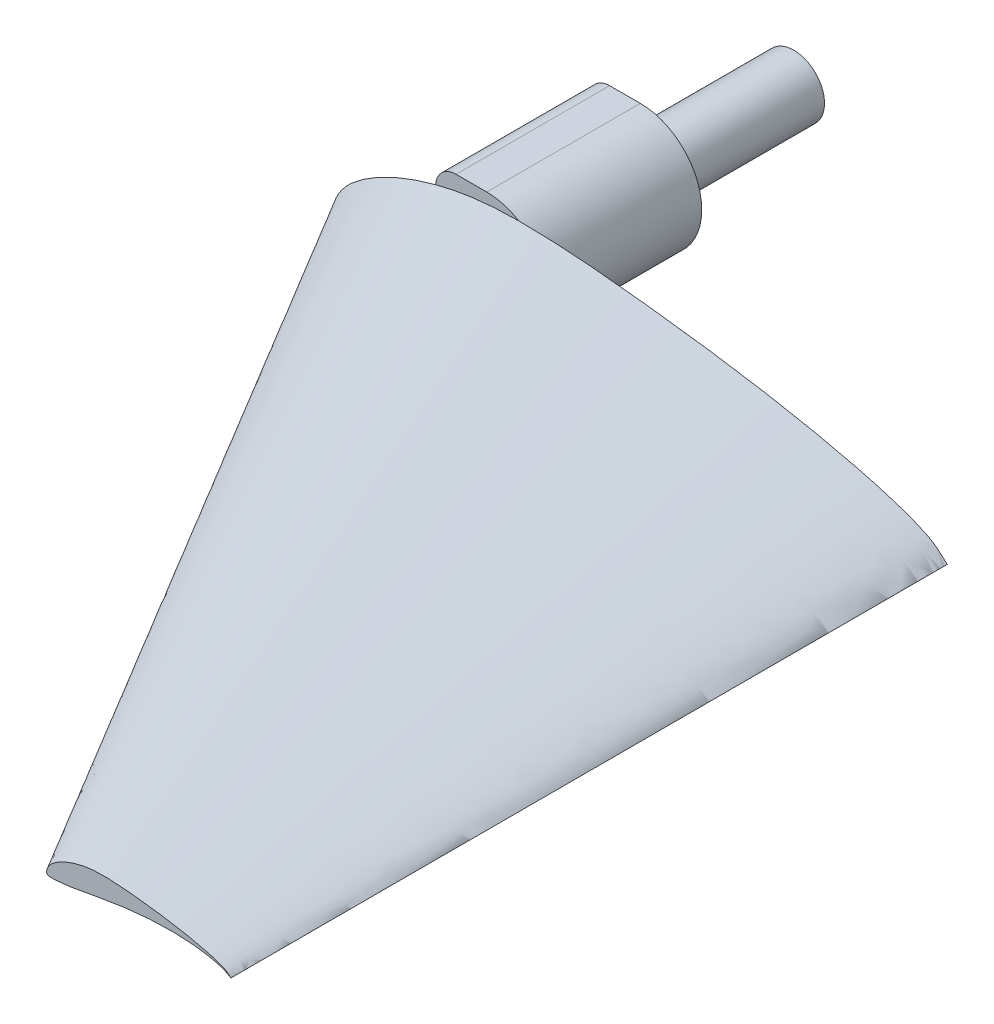
SolidWorks part; units mm, degrees
material "Nylon 101"
ref_plane "Front Plane" through (0, 0, 0) normal (0, 0, 1) x (1, 0, 0)
ref_plane "Top Plane" through (0, 0, 0) normal (0, 1, 0) x (1, 0, 0)
ref_plane "Right Plane" through (0, 0, 0) normal (1, 0, 0) x (0, 0, -1)
curve "Curve1"
  spline degree 3 poles (59.7678, 0.1558, 0) (60.0544, -0.0387, 0) (59.8031, 0.1485, 0) (59.6363, 0.3122, 0) (59.2659, 0.654, 0) (58.8289, 1.0177, 0) (58.2312, 1.3843, 0) (57.4879, 1.7396, 0) (56.5906, 2.1104, 0) (55.5406, 2.4917, 0) (54.3427, 2.8798, 0) (53.0045, 3.2753, 0) (51.5282, 3.6599, 0) (49.9319, 4.0656, 0) (48.2145, 4.4525, 0) (46.3922, 4.8372, 0) (44.4742, 5.2122, 0) (42.4721, 5.5744, 0) (40.3983, 5.9229, 0) (38.265, 6.2533, 0) (36.0858, 6.5663, 0) (33.8748, 6.8594, 0) (31.648, 7.1315, 0) (29.423, 7.3848, 0) (27.2185, 7.6127, 0) (25.0523, 7.811, 0) (22.9397, 7.9686, 0) (20.8927, 8.077, 0) (18.9227, 8.1238, 0) (17.0399, 8.1188, 0) (15.2476, 8.0266, 0) (13.5454, 7.8398, 0) (11.9261, 7.5756, 0) (10.3894, 7.2334, 0) (8.937, 6.8321, 0) (7.5748, 6.3788, 0) (6.3088, 5.8842, 0) (5.1469, 5.3508, 0) (4.0926, 4.7895, 0) (3.1518, 4.2068, 0) (2.3304, 3.6104, 0) (1.6286, 3.013, 0) (1.0568, 2.4081, 0) (0.6175, 1.801, 0) (0.293, 1.2104, 0) (0.0851, 0.6496, 0) (-0.014, 0.132, 0) (0.0051, -0.3058, 0) (0.1178, -0.7073, 0) (0.5368, -0.9066, 0) (1.1, -0.9346, 0) (1.8706, -0.9617, 0) (2.8397, -0.9199, 0) (3.9962, -0.8431, 0) (5.3274, -0.7201, 0) (6.8197, -0.5537, 0) (8.4657, -0.3402, 0) (10.2646, -0.0419, 0) (12.2253, 0.3321, 0) (14.3574, 0.7392, 0) (16.6507, 1.169, 0) (19.0906, 1.6038, 0) (21.6593, 2.0271, 0) (24.3369, 2.4248, 0) (27.1002, 2.7825, 0) (29.9244, 3.0895, 0) (32.7828, 3.3322, 0) (35.6468, 3.5043, 0) (38.4864, 3.5989, 0) (41.2709, 3.6108, 0) (43.9691, 3.5393, 0) (46.5501, 3.386, 0) (48.983, 3.153, 0) (51.2388, 2.849, 0) (53.288, 2.483, 0) (55.1067, 2.0673, 0) (56.6613, 1.6224, 0) (57.9337, 1.1476, 0) (58.8414, 0.7131, 0) (59.5107, 0.3113, 0) (59.7678, 0.1558, 0) (60.0544, -0.0387, 0) (59.8031, 0.1485, 0) knots -0.009748 -0.004147 -0.001 0 0.00098 0.003649 0.007484 0.012095 0.017526 0.024052 0.031783 0.040678 0.05071 0.061833 0.073978 0.087118 0.101144 0.11599 0.13157 0.147788 0.16455 0.181757 0.199311 0.217095 0.23499 0.252856 0.27054 0.287886 0.304773 0.321101 0.336806 0.3518 0.366031 0.379615 0.392653 0.40517 0.417171 0.428603 0.439419 0.449596 0.459102 0.467907 0.475988 0.483309 0.489874 0.495803 0.501149 0.505903 0.510046 0.513579 0.516447 0.51935 0.523823 0.529973 0.537715 0.546968 0.557637 0.56962 0.582804 0.597247 0.613135 0.630443 0.649056 0.668822 0.689595 0.711189 0.733426 0.756094 0.778988 0.80189 0.824566 0.846792 0.868338 0.888978 0.908492 0.926659 0.943286 0.958169 0.971136 0.981956 0.990252 0.995853 0.999 1 1.00098 1.003649 1.007484 periodic
sketch "Sketch2" plane through (0, 0, 0) normal (0, 0, 1) x (1, 0, 0)
  spline S0 degree 3 poles (59.7678, 0.1558) (60.0544, -0.0387) (59.8031, 0.1485) (59.6363, 0.3122) (59.2659, 0.654) (58.8289, 1.0177) (58.2312, 1.3843) (57.4879, 1.7396) (56.5906, 2.1104) (55.5406, 2.4917) (54.3427, 2.8798) (53.0045, 3.2753) (51.5282, 3.6599) (49.9319, 4.0656) (48.2145, 4.4525) (46.3922, 4.8372) (44.4742, 5.2122) (42.4721, 5.5744) (40.3983, 5.9229) (38.265, 6.2533) (36.0858, 6.5663) (33.8748, 6.8594) (31.648, 7.1315) (29.423, 7.3848) (27.2185, 7.6127) (25.0523, 7.811) (22.9397, 7.9686) (20.8927, 8.077) (18.9227, 8.1238) (17.0399, 8.1188) (15.2476, 8.0266) (13.5454, 7.8398) (11.9261, 7.5756) (10.3894, 7.2334) (8.937, 6.8321) (7.5748, 6.3788) (6.3088, 5.8842) (5.1469, 5.3508) (4.0926, 4.7895) (3.1518, 4.2068) (2.3304, 3.6104) (1.6286, 3.013) (1.0568, 2.4081) (0.6175, 1.801) (0.293, 1.2104) (0.0851, 0.6496) (-0.014, 0.132) (0.0051, -0.3058) (0.1178, -0.7073) (0.5368, -0.9066) (1.1, -0.9346) (1.8706, -0.9617) (2.8397, -0.9199) (3.9962, -0.8431) (5.3274, -0.7201) (6.8197, -0.5537) (8.4657, -0.3402) (10.2646, -0.0419) (12.2253, 0.3321) (14.3574, 0.7392) (16.6507, 1.169) (19.0906, 1.6038) (21.6593, 2.0271) (24.3369, 2.4248) (27.1002, 2.7825) (29.9244, 3.0895) (32.7828, 3.3322) (35.6468, 3.5043) (38.4864, 3.5989) (41.2709, 3.6108) (43.9691, 3.5393) (46.5501, 3.386) (48.983, 3.153) (51.2388, 2.849) (53.288, 2.483) (55.1067, 2.0673) (56.6613, 1.6224) (57.9337, 1.1476) (58.8414, 0.7131) (59.5107, 0.3113) (59.7678, 0.1558) (60.0544, -0.0387) (59.8031, 0.1485) knots -0.009748 -0.004147 -0.001 0 0.00098 0.003649 0.007484 0.012095 0.017526 0.024052 0.031783 0.040678 0.05071 0.061833 0.073978 0.087118 0.101144 0.11599 0.13157 0.147788 0.16455 0.181757 0.199311 0.217095 0.23499 0.252856 0.27054 0.287886 0.304773 0.321101 0.336806 0.3518 0.366031 0.379615 0.392653 0.40517 0.417171 0.428603 0.439419 0.449596 0.459102 0.467907 0.475988 0.483309 0.489874 0.495803 0.501149 0.505903 0.510046 0.513579 0.516447 0.51935 0.523823 0.529973 0.537715 0.546968 0.557637 0.56962 0.582804 0.597247 0.613135 0.630443 0.649056 0.668822 0.689595 0.711189 0.733426 0.756094 0.778988 0.80189 0.824566 0.846792 0.868338 0.888978 0.908492 0.926659 0.943286 0.958169 0.971136 0.981956 0.990252 0.995853 0.999 1 1.00098 1.003649 1.007484 only from (60, 0) to (60, 0) construction
  spline S1 degree 3 poles (59.7678, 0.1558) (60.0544, -0.0387) (59.8031, 0.1485) (59.6363, 0.3122) (59.2659, 0.654) (58.8289, 1.0177) (58.2312, 1.3843) (57.4879, 1.7396) (56.5906, 2.1104) (55.5406, 2.4917) (54.3427, 2.8798) (53.0045, 3.2753) (51.5282, 3.6599) (49.9319, 4.0656) (48.2145, 4.4525) (46.3922, 4.8372) (44.4742, 5.2122) (42.4721, 5.5744) (40.3983, 5.9229) (38.265, 6.2533) (36.0858, 6.5663) (33.8748, 6.8594) (31.648, 7.1315) (29.423, 7.3848) (27.2185, 7.6127) (25.0523, 7.811) (22.9397, 7.9686) (20.8927, 8.077) (18.9227, 8.1238) (17.0399, 8.1188) (15.2476, 8.0266) (13.5454, 7.8398) (11.9261, 7.5756) (10.3894, 7.2334) (8.937, 6.8321) (7.5748, 6.3788) (6.3088, 5.8842) (5.1469, 5.3508) (4.0926, 4.7895) (3.1518, 4.2068) (2.3304, 3.6104) (1.6286, 3.013) (1.0568, 2.4081) (0.6175, 1.801) (0.293, 1.2104) (0.0851, 0.6496) (-0.014, 0.132) (0.0051, -0.3058) (0.1178, -0.7073) (0.5368, -0.9066) (1.1, -0.9346) (1.8706, -0.9617) (2.8397, -0.9199) (3.9962, -0.8431) (5.3274, -0.7201) (6.8197, -0.5537) (8.4657, -0.3402) (10.2646, -0.0419) (12.2253, 0.3321) (14.3574, 0.7392) (16.6507, 1.169) (19.0906, 1.6038) (21.6593, 2.0271) (24.3369, 2.4248) (27.1002, 2.7825) (29.9244, 3.0895) (32.7828, 3.3322) (35.6468, 3.5043) (38.4864, 3.5989) (41.2709, 3.6108) (43.9691, 3.5393) (46.5501, 3.386) (48.983, 3.153) (51.2388, 2.849) (53.288, 2.483) (55.1067, 2.0673) (56.6613, 1.6224) (57.9337, 1.1476) (58.8414, 0.7131) (59.5107, 0.3113) (59.7678, 0.1558) (60.0544, -0.0387) (59.8031, 0.1485) knots -0.009748 -0.004147 -0.001 0 0.00098 0.003649 0.007484 0.012095 0.017526 0.024052 0.031783 0.040678 0.05071 0.061833 0.073978 0.087118 0.101144 0.11599 0.13157 0.147788 0.16455 0.181757 0.199311 0.217095 0.23499 0.252856 0.27054 0.287886 0.304773 0.321101 0.336806 0.3518 0.366031 0.379615 0.392653 0.40517 0.417171 0.428603 0.439419 0.449596 0.459102 0.467907 0.475988 0.483309 0.489874 0.495803 0.501149 0.505903 0.510046 0.513579 0.516447 0.51935 0.523823 0.529973 0.537715 0.546968 0.557637 0.56962 0.582804 0.597247 0.613135 0.630443 0.649056 0.668822 0.689595 0.711189 0.733426 0.756094 0.778988 0.80189 0.824566 0.846792 0.868338 0.888978 0.908492 0.926659 0.943286 0.958169 0.971136 0.981956 0.990252 0.995853 0.999 1 1.00098 1.003649 1.007484 only from (60, 0) to (60, 0)
ref_plane "Plane1" through (0, 0, 70) normal (0, 0, 1) x (1, 0, 0)
sketch "Sketch3" plane through (0, 0, 70) normal (0, 0, 1) x (1, 0, 0)
  spline S1 degree 3 poles (59.9303, 0.0467) (60.0163, -0.0116) (59.9409, 0.0445) (59.8909, 0.0936) (59.7798, 0.1962) (59.6487, 0.3053) (59.4694, 0.4153) (59.2464, 0.5219) (58.9772, 0.6331) (58.6622, 0.7475) (58.3028, 0.864) (57.9013, 0.9826) (57.4585, 1.098) (56.9796, 1.2197) (56.4644, 1.3358) (55.9177, 1.4512) (55.3423, 1.5636) (54.7416, 1.6723) (54.1195, 1.7769) (53.4795, 1.876) (52.8258, 1.9699) (52.1624, 2.0578) (51.4944, 2.1395) (50.8269, 2.2154) (50.1655, 2.2838) (49.5157, 2.3433) (48.8819, 2.3906) (48.2678, 2.4231) (47.6768, 2.4371) (47.112, 2.4356) (46.5743, 2.408) (46.0636, 2.3519) (45.5778, 2.2727) (45.1168, 2.17) (44.6811, 2.0496) (44.2724, 1.9136) (43.8927, 1.7653) (43.5441, 1.6052) (43.2278, 1.4369) (42.9455, 1.262) (42.6991, 1.0831) (42.4886, 0.9039) (42.317, 0.7224) (42.1852, 0.5403) (42.0879, 0.3631) (42.0255, 0.1949) (41.9958, 0.0396) (42.0015, -0.0917) (42.0353, -0.2122) (42.161, -0.272) (42.33, -0.2804) (42.5612, -0.2885) (42.8519, -0.276) (43.1989, -0.2529) (43.5982, -0.216) (44.0459, -0.1661) (44.5397, -0.1021) (45.0794, -0.0126) (45.6676, 0.0996) (46.3072, 0.2218) (46.9952, 0.3507) (47.7272, 0.4811) (48.4978, 0.6081) (49.3011, 0.7275) (50.13, 0.8347) (50.9773, 0.9269) (51.8348, 0.9997) (52.694, 1.0513) (53.5459, 1.0797) (54.3813, 1.0833) (55.1907, 1.0618) (55.965, 1.0158) (56.6949, 0.9459) (57.3716, 0.8547) (57.9864, 0.7449) (58.532, 0.6202) (58.9984, 0.4867) (59.3801, 0.3443) (59.6524, 0.2139) (59.8532, 0.0934) (59.9303, 0.0467) (60.0163, -0.0116) (59.9409, 0.0445) knots -0.009748 -0.004147 -0.001 0 0.00098 0.003649 0.007484 0.012095 0.017526 0.024052 0.031783 0.040678 0.05071 0.061833 0.073978 0.087118 0.101144 0.11599 0.13157 0.147788 0.16455 0.181757 0.199311 0.217095 0.23499 0.252856 0.27054 0.287886 0.304773 0.321101 0.336806 0.3518 0.366031 0.379615 0.392653 0.40517 0.417171 0.428603 0.439419 0.449596 0.459102 0.467907 0.475988 0.483309 0.489874 0.495803 0.501149 0.505903 0.510046 0.513579 0.516447 0.51935 0.523823 0.529973 0.537715 0.546968 0.557637 0.56962 0.582804 0.597247 0.613135 0.630443 0.649056 0.668822 0.689595 0.711189 0.733426 0.756094 0.778988 0.80189 0.824566 0.846792 0.868338 0.888978 0.908492 0.926659 0.943286 0.958169 0.971136 0.981956 0.990252 0.995853 0.999 1 1.00098 1.003649 1.007484 only from (60, 0) to (60, 0)
loft "Loft1" add profiles "Sketch3", "Sketch2" connector at (60, 0, 70) connector at (60, 0, 0)
sketch "Sketch5" plane through (0, 0, 0) normal (0, 0, 1) x (1, 0, 0)
  line L1 (10, 9) -> (15, 9)
  line L2 (10, 9) -> (10, -3)
  line L3 (10, -3) -> (15, -3)
  arc A0 (15, 9) -> (15, -3) centre (15, 3) cw
  dimension "D4" = 15
  dimension "D1" = 12
  dimension "D2" = 3
  dimension "D3" = 5
extrude "Boss-Extrude2" add sketch "Sketch5" against normal blind 15 contours A0 L3 L2 L1
sketch "Sketch6" plane through (0, 0, -15) normal (0, 0, -1) x (-1, 0, 0)
  circle A0 centre (-15, 3) radius 3
  dimension "D1" = 6
extrude "Boss-Extrude3" add sketch "Sketch6" along normal blind 15 contours A0
fillet "Fillet1" radius 2 2 edges at (10, -3, -7.5) (10, 9, -7.5)
